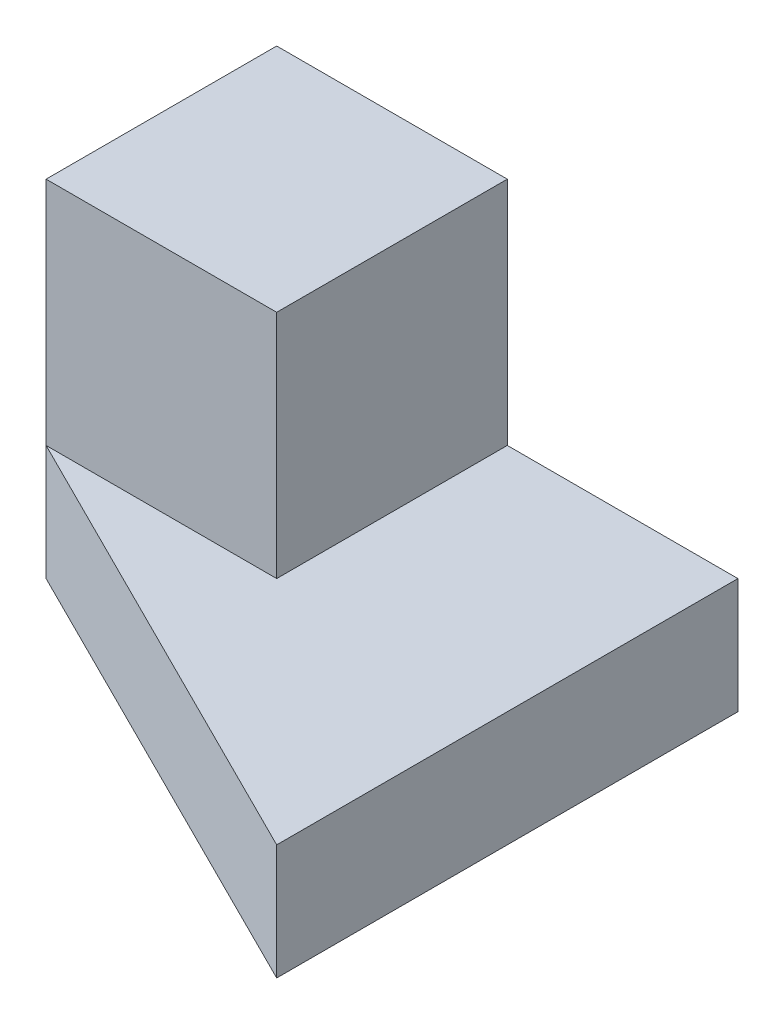
SolidWorks part; units mm, degrees
ref_plane "Front Plane" through (0, 0, 0) normal (0, 0, 1) x (1, 0, 0)
ref_plane "Top Plane" through (0, 0, 0) normal (0, 1, 0) x (1, 0, 0)
ref_plane "Right Plane" through (0, 0, 0) normal (1, 0, 0) x (0, 0, -1)
sketch "Sketch3" plane through (0, 0, 0) normal (0, 1, 0) x (1, 0, 0)
  line L0 (0, 0) -> (1016, 0)
  line L1 (1016, 0) -> (1016, -1016)
  line L2 (1016, -1016) -> (0, -508)
  line L3 (0, -508) -> (0, 0)
  line L4 (0, -508) -> (508, -508)
  line L5 (508, -508) -> (508, 0)
  dimension "D1" = 1016
  dimension "D2" = 1016
  dimension "D3" = 508
  dimension "D4" = 508
extrude "Boss-Extrude2" add sketch "Sketch3" along normal blind 254 contours L5 L4 L2 L1 L0 region at (719.6667, 0, 465.6667)
extrude "Boss-Extrude3" add sketch "Sketch3<3>" along normal blind 762 contours L4 L5 L0 L3 region at (254, 0, 254)
sketch "Sketch3<3>" plane through (0, 0, 0) normal (0, 1, 0) x (1, 0, 0) same geometry as "Sketch3"
